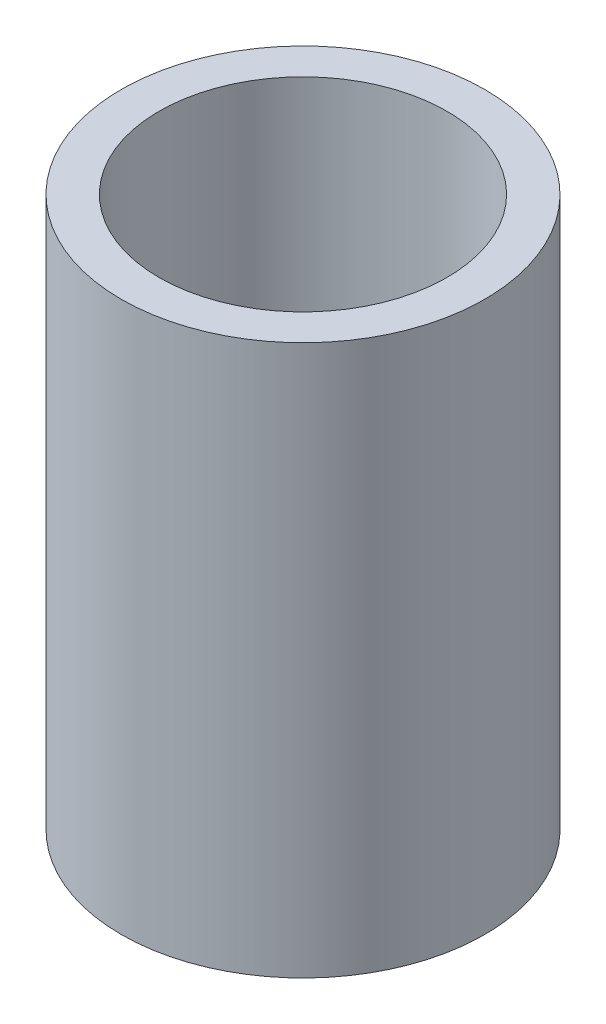
SolidWorks part; units mm, degrees
ref_plane "Front Plane" through (0, 0, 0) normal (0, 0, 1) x (1, 0, 0)
ref_plane "Top Plane" through (0, 0, 0) normal (0, 1, 0) x (1, 0, 0)
ref_plane "Right Plane" through (0, 0, 0) normal (1, 0, 0) x (0, 0, -1)
sketch "Sketch1" plane through (0, 0, 0) normal (0, 1, 0) x (1, 0, 0)
  circle A0 centre (0, 0) radius 27.5
  dimension "SLEEVE_OD" = 55
extrude "Boss-Extrude1" add sketch "Sketch1" along normal blind 83.2442
sketch "Sketch2" plane through (0, 0, 0) normal (0, 1, 0) x (1, 0, 0)
  circle A0 centre (0, 0) radius 21.7866
  dimension "BORE_D" = 43.5732
extrude "Cut-Extrude1" cut sketch "Sketch2" along normal through all
chamfer "Chamfer1" distance 3.7109 angle 45 rebuild error yes
